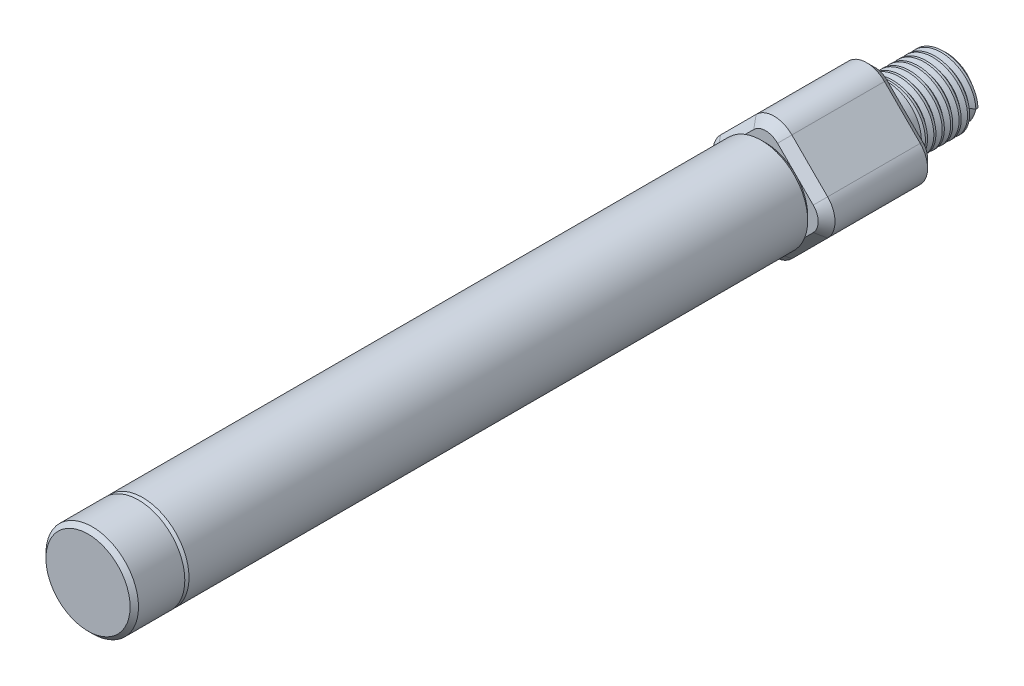
SolidWorks part; units mm, degrees
ref_plane "正面" through (0, 0, 0) normal (0, 0, 1) x (1, 0, 0)
ref_plane "平面" through (0, 0, 0) normal (0, 1, 0) x (1, 0, 0)
ref_plane "右側面" through (0, 0, 0) normal (1, 0, 0) x (0, 0, -1)
sketch "ｽｹｯﾁ1" plane through (0, 0, 0) normal (0, 0, 1) x (1, 0, 0)
  circle A0 centre (0, 0) radius 5.5
  dimension "D1" = 11
extrude "ﾎﾞｽ - 押し出し1" add sketch "ｽｹｯﾁ1" along normal blind 74.5
chamfer "面取り1" distance 0.5 angle 45 2 edges at (5.5, 0, 74.5) (5.5, 0, 0)
sketch "ｽｹｯﾁ2" plane through (0, 0, 74.5) normal (0, 0, 1) x (1, 0, 0)
  circle A0 centre (0, 0) radius 5.5
  dimension "D1" = 11
extrude "ﾎﾞｽ - 押し出し2" add sketch "ｽｹｯﾁ2" along normal blind 6
chamfer "面取り2" distance 0.5 angle 45 1 edges at (5.5, 0, 80.5)
sketch "ｽｹｯﾁ3" plane through (0, 0, 0) normal (0, 0, -1) x (-1, 0, 0)
  line L1 (8.4853, 0) -> (0, 8.4853)
  line L2 (0, 8.4853) -> (-8.4853, 0)
  line L3 (-8.4853, 0) -> (0, -8.4853)
  line L4 (0, -8.4853) -> (8.4853, 0)
  circle A0 centre (0, 0) radius 6 construction
  dimension "D1" = 12
extrude "ﾎﾞｽ - 押し出し3" add sketch "ｽｹｯﾁ3" along normal blind 13
fillet "ﾌｨﾚｯﾄ1" radius 3 4 edges at (0, 8.4853, -6.5) (8.4853, 0, -6.5) (0, -8.4853, -6.5) (-8.4853, 0, -6.5)
chamfer "面取り5" distance 1 angle 45 16 edges at (4.2426, 4.2426, 0) (7.2426, 0, 0) (0, 7.2426, 0) (4.2426, -4.2426, 0) (-4.2426, 4.2426, 0) (0, -7.2426, 0) (-7.2426, 0, 0) (-4.2426, -4.2426, 0) (-7.2426, 0, -13) (-4.2426, -4.2426, -13) (0, -7.2426, -13) (4.2426, -4.2426, -13) (7.2426, 0, -13) (4.2426, 4.2426, -13) (0, 7.2426, -13) (-4.2426, 4.2426, -13)
sketch "ｽｹｯﾁ4" plane through (0, 0, -13) normal (0, 0, -1) x (-1, 0, 0)
  circle A0 centre (0, 0) radius 4
  dimension "D1" = 8
extrude "ﾎﾞｽ - 押し出し4" add sketch "ｽｹｯﾁ4" along normal blind 1.5
sketch "ｽｹｯﾁ6" plane through (0, 0, -14.5) normal (0, 0, -1) x (-1, 0, 0)
  circle A0 centre (0, 0) radius 3.5
  dimension "D1" = 7
extrude "ﾎﾞｽ - 押し出し5" add sketch "ｽｹｯﾁ6" along normal blind 7
thread "ねじ山1" pitch 1 method extrude profile "ねじ山の輪郭1" start angle 0, offset 0, length 7, pitch 1, diameter 7
ref_plane "平面1" through (3.5, 0, -21.5) normal (0, 1, 0) x (-1, 0, 0)
sketch "ねじ山の輪郭1" plane through (3.5, 0, -21.5) normal (0, 1, 0) x (-1, 0, 0)
  line L0 (0, 0) -> (0, 1) construction
  line L11 (0, 0) -> (0, 0.875)
  line L12 (0, 0.875) -> (-0.5413, 0.5625)
  line L13 (-0.5413, 0.5625) -> (-0.5413, 0.3125)
  line L15 (-0.5413, 0.3125) -> (0, 0)
  line L17 (-0.5413, 0.4375) -> (0, 0.4375) construction
  point P2 (0, 0)
  dimension "Pitch" = 1
  dimension "Profile_Angle" = 60
  dimension "Profile_Land" = 0.25
  dimension "Profile_Height" = 0.5413
sketch "ｽｹｯﾁ9" plane through (0, 0, -21.5) normal (0, 0, -1) x (-1, 0, 0)
  circle A0 centre (0, 0) radius 2
  dimension "D1" = 4
extrude "ｶｯﾄ - 押し出し1" cut sketch "ｽｹｯﾁ9" against normal blind 80
